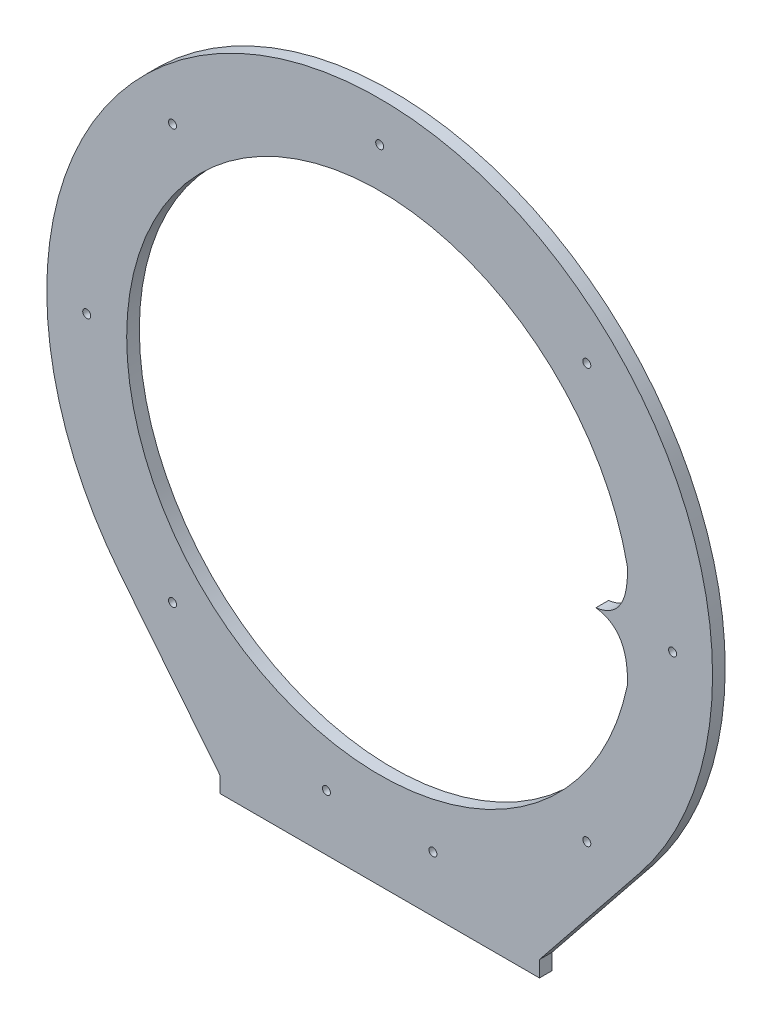
SolidWorks part; units mm, degrees
note: '?' marks a value the reader was unsure of.
ref_plane "Front Plane" through (0, 0, 0) normal (0, 0, 1) x (1, 0, 0)
ref_plane "Top Plane" through (0, 0, 0) normal (0, 1, 0) x (1, 0, 0)
ref_plane "Right Plane" through (0, 0, 0) normal (1, 0, 0) x (0, 0, -1)
sketch "Sketch1" plane through (0, 0, 0) normal (0, 0, 1) x (1, 0, 0)
  line L0 (0, -95) -> (0, -125) construction
  line L1 (-95, 0) -> (95, 0) construction
  line L2 (-67.1751, -67.1751) -> (67.1751, 67.1751) construction
  line L3 (-67.1751, 67.1751) -> (67.1751, -67.1751) construction
  line L4 (67.1751, -67.1751) -> (88.3883, -88.3883) construction
  line L5 (67.1751, 67.1751) -> (88.3883, 88.3883) construction
  line L6 (0, 95) -> (0, -95) construction
  line L7 (95, 0) -> (125, 0) construction
  line L8 (93.0158, 19.3149) -> (93.7029, 1.7225) construction
  line L9 (93.7029, 1.7225) -> (81.198, 0) construction
  line L10 (93.0158, -19.3149) -> (93.7029, -1.7225) construction
  line L11 (93.7029, -1.7225) -> (81.198, 0) construction
  line L23 (-60, -125) -> (-97.5293, -78.186)
  line L30 (-60, -125) -> (-60, -131)
  line L31 (-60, -131) -> (60, -131)
  line L32 (60, -125) -> (60, -131)
  line L33 (-60, -125) -> (60, -131) construction
  line L34 (-60, -131) -> (60, -125) construction
  line L35 (60, -125) -> (97.5293, -78.186)
  line L36 (-60, -125) -> (60, -125) construction
  arc A0 (93.0158, 19.3149) -> (93.0158, -19.3149) centre (0, 0) ccw
  circle A3 centre (77.7817, -77.7817) radius 1.5
  circle A5 centre (77.7817, 77.7817) radius 1.5
  circle A6 centre (-77.7817, -77.7817) radius 1.5
  circle A7 centre (0, 110) radius 1.5
  circle A8 centre (-77.7817, 77.7817) radius 1.5
  circle A9 centre (110, 0) radius 1.5
  circle A10 centre (-110, 0) radius 1.5
  arc A22 (88.3883, -88.3883) -> (-97.5293, -78.186) centre (0, 0) ccw
  circle A23 centre (-20, -110) radius 1.5
  circle A24 centre (20, -110) radius 1.5
  spline S0 degree 2 poles (93.0158, 19.3149) (93.7029, 1.7225) (81.198, 0) knots 0 0 0 1 1 1
  spline S1 degree 2 poles (93.0158, -19.3149) (93.7029, -1.7225) (81.198, 0) knots 0 0 0 1 1 1
  point P1 (0, -128)
  point P3 (0, -128)
  point P11 (0, 0)
  point P14 (0, 0)
  point P31 (0, -128)
  point P47 (0, -125)
  point P55 (-67.1751, -105.4158)
  dimension "D1" = 15
  dimension "D2" = 15
  dimension "D7" = 15
  dimension "D4" = 20
  dimension "D3" = 15
  dimension "D5" = 15
  dimension "D6" = 3
extrude "Boss-Extrude1" add sketch "Sketch1" along normal blind 4.75
convert to sheet metal "Convert-Solid1" [suppressed] bend radius? 10 thickness? 4.75
sketch "Bend-Lines1" [suppressed] plane through (0, 0, 0) normal (0, 1, 0) x (1, 0, 0)
sketch "Bounding-Box1" [suppressed] plane through (0, 0, 0) normal (0, 1, 0) x (1, 0, 0)
sheet metal parameters "Sheet-Metal2" thickness 4.75 parameters "D1"=10
flat pattern "Flat-Pattern2" [suppressed]
sketch "Bend-Lines2" plane through (0, 0, 0) normal (0, 1, 0) x (1, 0, 0)
sketch3d "Bounding-Box2" [suppressed]
  line L0 (125, 125, 0) -> (125, -131, 0) construction
  line L1 (-125, 125, 0) -> (-125, -131, 0) construction
  line L2 (125, 125, 0) -> (-125, 125, 0) construction
  line L3 (125, -131, 0) -> (-125, -131, 0) construction
